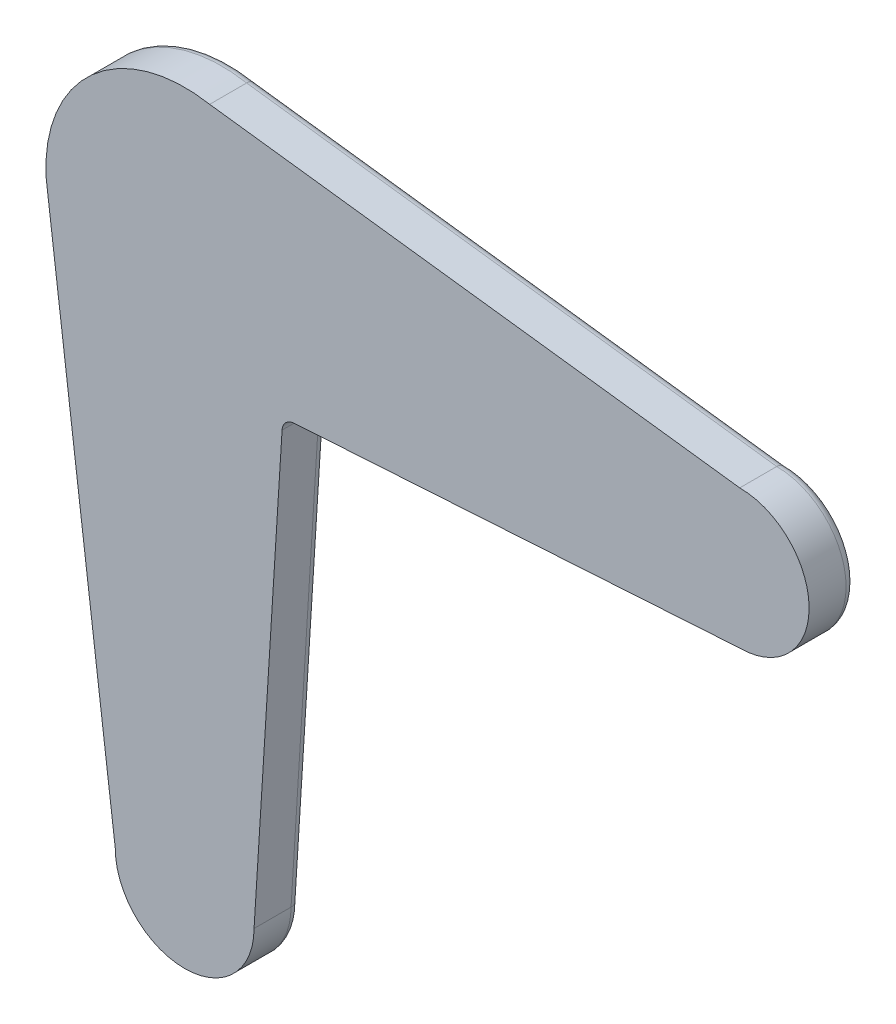
SolidWorks part; units mm, degrees
ref_plane "Front Plane" through (0, 0, 0) normal (0, 0, 1) x (1, 0, 0)
ref_plane "Top Plane" through (0, 0, 0) normal (0, 1, 0) x (1, 0, 0)
ref_plane "Right Plane" through (0, 0, 0) normal (1, 0, 0) x (0, 0, -1)
sketch "Sketch1" plane through (0, 0, 0) normal (0, 0, 1) x (1, 0, 0)
  line L0 (0, 600) -> (600, 0) construction
  line L1 (0, 0) -> (600, 0) construction
  line L2 (0, 0) -> (0, 600) construction
  line L3 (0, 600) -> (600, 600) construction
  line L4 (600, 0) -> (600, 600) construction
  line L5 (75, 0) -> (106.066, 493.934)
  line L6 (106.066, 493.934) -> (600, 525)
  line L7 (-75, 0) -> (-147.5495, 572.9974)
  line L8 (0, 600) -> (-106.066, 706.066) construction
  line L9 (-147.5495, 572.9974) -> (27.0026, 747.5495) construction
  line L10 (27.0026, 747.5495) -> (600, 675)
  circle A2 centre (0, 0) radius 75
  circle A3 centre (600, 600) radius 75
  circle A4 centre (0, 600) radius 150
  circle A5 centre (119.0901, 480.9099) radius 13.8159
extrude "Boss-Extrude1" add sketch "Sketch1" along normal blind 50 contours A4 | A4 L7 A2 L5 | A4 L6 A3 L10 | A3 | A2 | A5 L6 L5 region at (-11.2961, 277.8482, 0) region at (0, 0, 0) region at (108.5663, 491.4337, 0) region at (322.1518, 611.2961, 0) region at (0, 600, 0) region at (600, 600, 0)
sketch "Sketch2" plane through (0, 0, 0) normal (0, 0, -1) x (-1, 0, 0)
  line L0 (-109.3208, 490.6792) -> (106.066, 706.066) construction
  arc A1 (-105.3014, 481.7771) -> (-118.2229, 494.6986) centre (-119.0901, 480.9099) ccw construction
  arc A2 (147.5495, 572.9974) -> (-27.0026, 747.5495) centre (0, 600) ccw construction
  circle A3 centre (-1.6274, 598.3726) radius 85
extrude "Boss-Extrude2" add sketch "Sketch2" along normal blind 50
fillet "Fillet2" radius 40 1 edges at (86.6274, 598.3726, 0)
fillet "Fillet3" radius 10 8 edges at (-111.2748, 286.4987, 0) (0, -75, 0) (675, 600, 0) (109.3208, 490.6792, 0) (90.1507, 240.8886, 0) (359.1114, 509.8493, 0) (-106.066, 706.066, 0) (313.5013, 711.2748, 0)
sketch "Sketch3" plane through (0, 0, -50) normal (0, 0, -1) x (-1, 0, 0)
  line L0 (-1.6274, 683.3726) -> (-1.6274, 513.3726) construction
  line L2 (-46.6274, 643.3726) -> (43.3726, 643.3726)
  line L3 (-46.6274, 643.3726) -> (-46.6274, 553.3726)
  line L4 (-46.6274, 553.3726) -> (43.3726, 553.3726)
  line L5 (43.3726, 643.3726) -> (43.3726, 553.3726)
  line L6 (-46.6274, 643.3726) -> (43.3726, 553.3726) construction
  line L7 (-46.6274, 553.3726) -> (43.3726, 643.3726) construction
  circle A0 centre (-1.6274, 598.3726) radius 85 construction
  point P5 (-1.6274, 598.3726)
extrude "Cut-Extrude2" cut sketch "Sketch3" against normal blind 50
